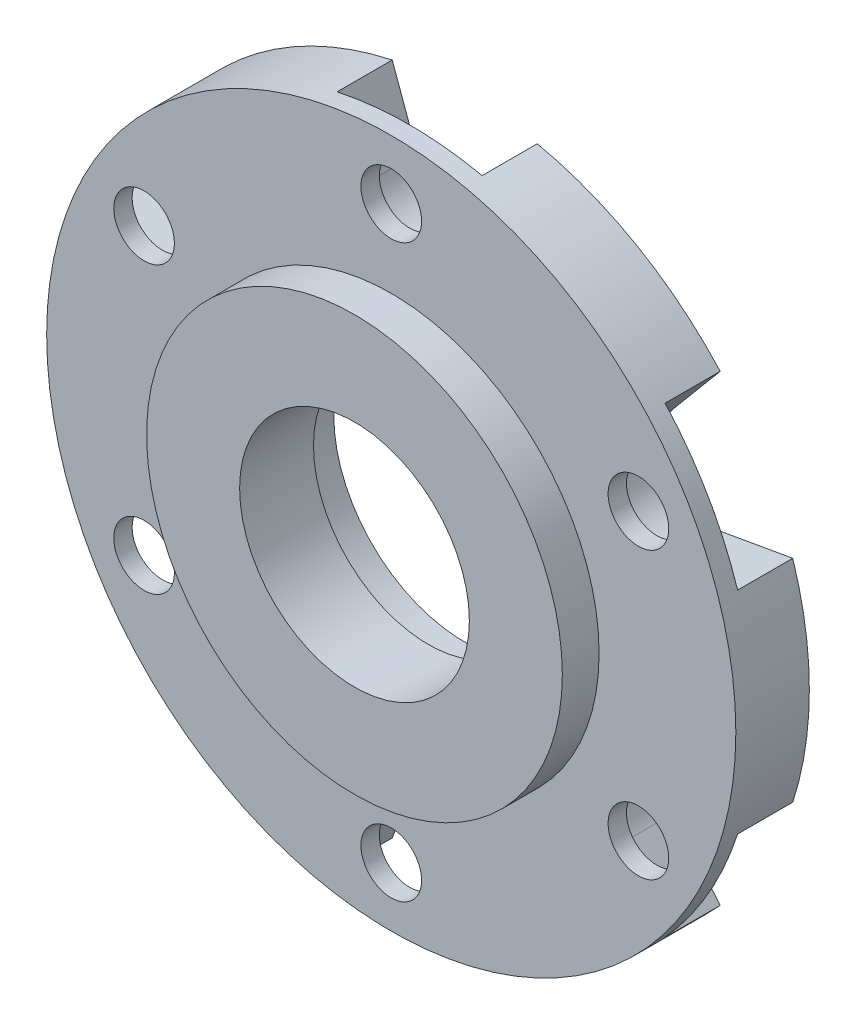
SolidWorks part; units mm, degrees
material "6061-T6 (SS)"
ref_plane "Front Plane" through (0, 0, 0) normal (0, 0, 1) x (1, 0, 0)
ref_plane "Top Plane" through (0, 0, 0) normal (0, 1, 0) x (1, 0, 0)
ref_plane "Right Plane" through (0, 0, 0) normal (1, 0, 0) x (0, 0, -1)
sketch "Sketch Spindle Skeleton" plane through (0, 0, 0) normal (1, 0, 0) x (0, 0, -1)
  line L0 (-108, -9.5) -> (-149, -9.5)
  line L5 (-1000, 0) -> (49000, 0)
  line L6 (0, -9.5) -> (0, 9.5)
  line L13 (0, 9.5) -> (-46.4, 9.5)
  line L26 (-46.4, 9.5) -> (-46.4, 14)
  line L27 (-46.4, 14) -> (-108, 14)
  line L32 (-108, 14) -> (-108, 9.5)
  line L34 (-165, 7) -> (-165, -7)
  line L36 (-108, -9.5) -> (-108, -14)
  line L37 (-108, -14) -> (-46.4, -14)
  line L38 (-46.4, -14) -> (-46.4, -9.5)
  line L39 (0, -9.5) -> (-46.4, -9.5)
  line L40 (-22.625, 37.5) -> (-14.625, 37.5)
  line L41 (-124.6, 22.6187) -> (-108, 22.6187)
  line L42 (-124.6, 22.6187) -> (-124.6, -22.6187)
  line L43 (-124.6, -22.6187) -> (-108, -22.6187)
  line L44 (-108, 22.6187) -> (-108, -22.6187)
  line L45 (-124.6, 22.6187) -> (-108, -22.6187) construction
  line L46 (-124.6, -22.6187) -> (-108, 22.6187) construction
  line L47 (-29.8, 22.6187) -> (-46.4, 22.6187)
  line L48 (-29.8, 22.6187) -> (-29.8, -22.6187)
  line L49 (-29.8, -22.6187) -> (-46.4, -22.6187)
  line L50 (-46.4, 22.6187) -> (-46.4, -22.6187)
  line L51 (-29.8, 22.6187) -> (-46.4, -22.6187) construction
  line L52 (-29.8, -22.6187) -> (-46.4, 22.6187) construction
  line L59 (-14.625, 37.5) -> (-14.625, -37.5)
  line L60 (-14.625, -37.5) -> (-22.625, -37.5)
  line L61 (-22.625, -22.6187) -> (-26.625, -22.6187)
  line L62 (-26.625, -22.6187) -> (-26.625, -12.5)
  line L63 (-26.625, -12.5) -> (-22.625, -12.5)
  line L64 (-22.625, -12.5) -> (-22.625, 12.5)
  line L65 (-22.625, 12.5) -> (-26.625, 12.5)
  line L66 (-26.625, 12.5) -> (-26.625, 22.6187)
  line L67 (-26.625, 22.6187) -> (-22.625, 22.6187)
  line L68 (-22.625, 22.6187) -> (-22.625, 37.5)
  line L69 (-22.625, -22.6187) -> (-22.625, -37.5)
  line L71 (-136.284, 37.5) -> (-23.625, 37.5)
  line L72 (-136.284, 37.5) -> (-136.284, -37.5)
  line L73 (-136.284, -37.5) -> (-23.625, -37.5)
  line L74 (-23.625, 37.5) -> (-23.625, -37.5)
  line L75 (-136.284, 37.5) -> (-23.625, -37.5) construction
  line L76 (-136.284, -37.5) -> (-23.625, 37.5) construction
  line L77 (-149, -9.5) -> (-149, -7)
  line L78 (-149, -7) -> (-165, -7)
  line L79 (-108, 9.5) -> (-149, 9.5)
  line L80 (-149, 7) -> (-165, 7)
  line L81 (-149, 9.5) -> (-149, 7)
  line L82 (-128.5, 9.5) -> (-128.5, -9.5) construction
  line L83 (-23.2, 9.5) -> (-23.2, -9.5) construction
  line L96 (-136.284, 37.5) -> (-144.284, 37.5)
  line L98 (-136.284, -37.5) -> (-144.284, -37.5)
  line L99 (-144.284, 37.5) -> (-144.284, -37.5)
  line L110 (-136.284, 37.5) -> (-136.284, -37.5)
  point P3 (0, 0)
  point P18 (-116.3, 0)
  point P24 (-38.1, 0)
  point P29 (-79.9545, 0)
  point P48 (-14.625, 31.0593)
  point P70 (-144.284, 31.0593)
revolve "Main Revolve" add sketch "Sketch Spindle Skeleton" angle 360 about L5 region at (0, 23.2432, 18.8195) region at (0, 17.5594, 25.125)
sketch "Sketch Center Cut" plane through (0, 0, 22.625) normal (0, 0, 1) x (1, 0, 0)
  circle A0 centre (0, 0) radius 12.5 construction
  circle A1 centre (0, 0) radius 12.5 construction
  circle A2 centre (0, 0) radius 12.5
  dimension "D1" = 25
extrude "Cut Center" cut sketch "Sketch Center Cut" against normal through all
hole_wizard "CBORE for M6 SHCS1" positions "Hole wizard sketch 1" profile "Hole wizard sketch 2" counterbore size "M6" standard "ANSI Metric" end condition through all
sketch "Hole wizard sketch 1" plane through (0, 0, 14.625) normal (0, 0, -1) x (-1, 0, 0)
  point P0 (0, 31.0593)
sketch "Hole wizard sketch 2" plane through (0, 31.0593, 14.625) normal (1, 0, 0) x (0, 1, 0)
  line L0 (0, 0) -> (0, 12)
  line L1 (0, 12) -> (3.3, 12)
  line L3 (3.3, 12) -> (3.3, 6)
  line L4 (3.3, 6) -> (5.5, 6)
  line L5 (5.5, 6) -> (5.5, 0)
  line L7 (5.5, 0) -> (0, 0)
  line L11 (0, -6.35) -> (0, 107.95) construction
  dimension "Thru Hole Dia." = 6.6
  dimension "Thru Hole Depth" = 12
  dimension "C'Bore Dia." = 11
  dimension "C'Bore Depth" = 6
pattern_circular "CirPattern1" count 6 over 360 about axis through (0, 0, 14.625) along (0, 0, 1) of "CBORE for M6 SHCS1"
sketch "Sketch1" plane through (0, 0, 14.625) normal (0, 0, -1) x (-1, 0, 0)
  circle A0 centre (0, 0) radius 14.2558
  dimension "D1" = 28.5115
extrude "Cut-Extrude1" cut sketch "Sketch1" against normal blind 3.9624
sketch "Sketch2" plane through (0, 0, 14.625) normal (0, 0, -1) x (-1, 0, 0)
  line L0 (-5.1683, 29.1782) -> (-7.8915, 36.6602)
  line L1 (0, 31.0593) -> (0, 37.5) construction
  line L2 (5.1683, 29.1782) -> (7.8915, 36.6602)
  line L3 (22.6849, 19.065) -> (27.8029, 25.1644)
  line L4 (27.8533, 10.1132) -> (35.6945, 11.4959)
  line L5 (27.8533, -10.1132) -> (35.6945, -11.4959)
  line L6 (22.6849, -19.065) -> (27.8029, -25.1644)
  line L7 (5.1683, -29.1782) -> (7.8915, -36.6602)
  line L8 (-5.1683, -29.1782) -> (-7.8915, -36.6602)
  line L9 (-22.6849, -19.065) -> (-27.8029, -25.1644)
  line L10 (-27.8533, -10.1132) -> (-35.6945, -11.4959)
  line L11 (-27.8533, 10.1132) -> (-35.6945, 11.4959)
  line L12 (-22.6849, 19.065) -> (-27.8029, 25.1644)
  circle A0 centre (0, 31.0593) radius 5.5 construction
  circle A1 centre (0, 0) radius 37.5 construction
  arc A2 (-5.1683, 29.1782) -> (5.1683, 29.1782) centre (0, 31.0593) ccw
  circle A3 centre (0, 0) radius 37.5
  arc A4 (22.6849, 19.065) -> (27.8533, 10.1132) centre (26.8982, 15.5297) ccw
  arc A5 (27.8533, -10.1132) -> (22.6849, -19.065) centre (26.8982, -15.5297) ccw
  arc A6 (5.1683, -29.1782) -> (-5.1683, -29.1782) centre (0, -31.0593) ccw
  arc A7 (-22.6849, -19.065) -> (-27.8533, -10.1132) centre (-26.8982, -15.5297) ccw
  arc A8 (-27.8533, 10.1132) -> (-22.6849, 19.065) centre (-26.8982, 15.5297) ccw
  point P37 (0, 0)
  circle M3 centre (-26.8982, 15.5297) radius 5.5
  circle M4 centre (-26.8982, -15.5297) radius 5.5
  circle M5 centre (0, -31.0593) radius 5.5
  circle M6 centre (26.8982, -15.5297) radius 5.5
  circle M7 centre (26.8982, 15.5297) radius 5.5
  circle M8 centre (0, 31.0593) radius 5.5
  circle M9 centre (0, 0) radius 37.5
  dimension "D1" = 20
  dimension "D2" = 6
extrude "Cut-Extrude2" cut sketch "Sketch2" against normal up to surface (6 mm away) contours M8 | L1 L2 M8 M9 | L1 A3 L0 M8 | L4 L3 M7 M9 | M7 | L6 L5 M6 M9 | M6 | M5 | L8 L7 M5 M9 | L10 L9 M4 M9 | M4 | L12 L11 M3 M9 | A3 M3 region at (4.3779, 34.1248, 14.625) region at (4.7535, 35.3844, 14.625) region at (-4.7535, 35.3844, 14.625) region at (25.3963, 21.9868, 14.625) region at (26.8982, 15.5297, 14.625) region at (-32.3037, 18.6505, 14.625) region at (31.7393, -11.0005, 14.625) region at (-26.8982, 15.5297, 14.625) region at (26.8982, -15.5297, 14.625) region at (6.3623, -32.9803, 14.625) region at (-32.3037, -18.6505, 14.625) region at (0, -31.0593, 14.625) region at (-26.8982, -15.5297, 14.625) up to face at (23.5982, -15.5297, 20.625)
